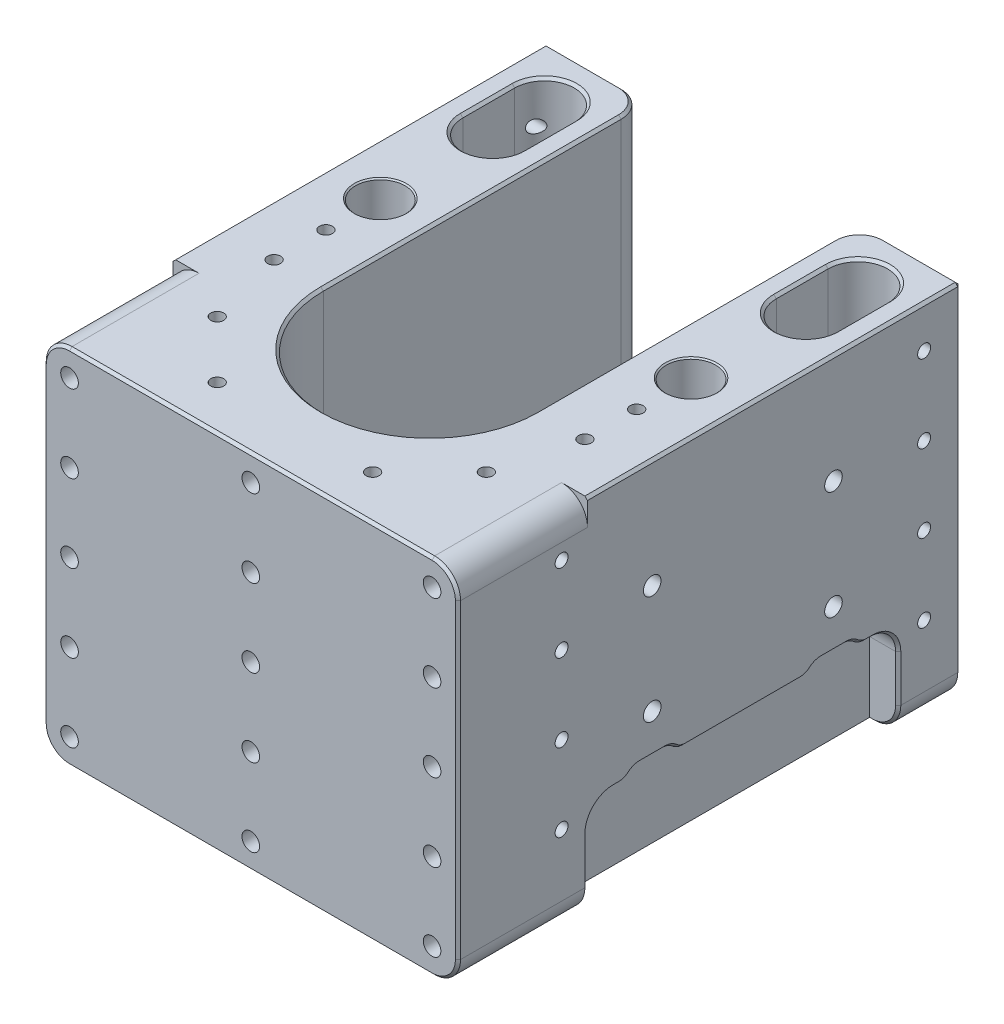
SolidWorks part; units mm, degrees
material "6061-T6 Aluminum"
ref_plane "Front Plane" through (0, 0, 0) normal (0, 0, 1) x (1, 0, 0)
ref_plane "Top Plane" through (0, 0, 0) normal (0, 1, 0) x (1, 0, 0)
ref_plane "Right Plane" through (0, 0, 0) normal (1, 0, 0) x (0, 0, -1)
sketch "Sketch1" plane through (0, 0, 0) normal (0, 1, 0) x (1, 0, 0)
  line L0 (41, 97) -> (80, 97)
  line L1 (-80, -97) -> (80, -97)
  line L2 (-80, -97) -> (-80, 97)
  line L3 (-80, 97) -> (-41, 97)
  line L4 (80, -97) -> (80, 97)
  line L5 (-41, 97) -> (0, 97) construction
  line L6 (0, 97) -> (41, 97) construction
  line L7 (-41, 97) -> (-41, -28)
  line L9 (41, -28) -> (41, 97)
  line L10 (-80, 0) -> (0, 0) construction
  line L11 (0, 0) -> (80, 0) construction
  line L12 (0, -69) -> (0, -97) construction
  arc A2 (-41, -28) -> (41, -28) centre (0, -28) ccw
  point P0 (0, 0)
  dimension "D1" = 160
  dimension "D2" = 194
  dimension "D3" = 28
  dimension "D4" = 82
extrude "Boss-Extrude1" add sketch "Sketch1" along normal blind 140
sketch "Sketch3" plane through (0, 140, 0) normal (0, 1, 0) x (1, 0, 0)
  line L0 (0, 0) -> (0, 13) construction
  line L3 (-60, 13) -> (60, 13) construction
  circle A4 centre (-60, 13) radius 9.55
  circle A5 centre (60, 13) radius 9.55
  dimension "D1" = 13
  dimension "D2" = 120
  dimension "D3" = 19.1
extrude "Cut-Extrude2" cut sketch "Sketch3" against normal blind 14.326 contours A4 | A5 region at (-60, 140, -13) region at (60, 140, -13)
sketch "Sketch8" plane through (80, 0, 0) normal (1, 0, 0) x (0, 0, -1)
  arc A0 (48, 102.25) -> (48, 93.75) centre (48, 98) ccw construction
  arc A1 (-22, 102.25) -> (-22, 93.75) centre (-22, 98) ccw construction
  arc A2 (-22, 60.25) -> (-22, 51.75) centre (-22, 56) ccw construction
  arc A3 (48, 60.25) -> (48, 51.75) centre (48, 56) ccw construction
  arc A4 (48, 102.25) -> (48, 93.75) centre (48, 98) ccw construction
  arc A5 (-22, 102.25) -> (-22, 93.75) centre (-22, 98) ccw construction
  arc A6 (-22, 60.25) -> (-22, 51.75) centre (-22, 56) ccw construction
  arc A7 (48, 60.25) -> (48, 51.75) centre (48, 56) ccw construction
hole_wizard "M8x1.25 Tapped Hole1" positions "Sketch11" profile "Sketch10" tap size "M8x1.25" standard "ANSI Metric"
sketch "Sketch11" plane through (80, 0, 0) normal (1, 0, 0) x (0, 0, -1)
  point P0 (48, 56)
  point P3 (-22, 56)
  point P6 (-22, 98)
  point P9 (48, 98)
cosmetic thread "Hole Thread2" parameters "D1"=25, "D2"=8
cosmetic thread "Hole Thread3" parameters "D1"=25, "D2"=8
cosmetic thread "Hole Thread4" parameters "D1"=25, "D2"=8
cosmetic thread "Hole Thread5" parameters "D1"=25, "D2"=8
sketch "Sketch10" plane through (80, 56, -48) normal (0, 1, 0) x (0, 0, -1)
  line L0 (0, 0) -> (0, 32.0429)
  line L1 (0, 32.0429) -> (3.4, 30)
  line L2 (3.4, 30) -> (3.4, 0)
  line L5 (3.4, 0) -> (0, 0)
  line L10 (0, 32.0429) -> (-3.4, 30) construction
  line L11 (0, -6.35) -> (0, 107.95) construction
  dimension "Tap Drill Dia." = 6.8
  dimension "Tap Drill Depth" = 30
  dimension "Drill Angle" = 118
mirror "Mirror2" about plane through (0, 0, 0) normal (1, 0, 0) of "M8x1.25 Tapped Hole1"
sketch "Sketch33" plane through (0, 0, 97) normal (0, 0, 1) x (1, 0, 0)
  line L0 (-80, 140) -> (-80, 0) construction
  line L1 (-70, 0) -> (70, 0)
  line L2 (-80, 10) -> (-80, 130)
  line L3 (-70, 140) -> (70, 140)
  line L4 (80, 10) -> (80, 130)
  line L5 (-70, 100) -> (-70, 70) construction
  line L6 (-70, 130) -> (-70, 100) construction
  line L7 (-70, 70) -> (-70, 40) construction
  line L8 (-70, 40) -> (-70, 10) construction
  line L9 (-80, 140) -> (80, 140) construction
  arc A0 (-70, 0) -> (-80, 10) centre (-70, 10) cw
  arc A1 (70, 0) -> (80, 10) centre (70, 10) ccw
  arc A2 (70, 140) -> (80, 130) centre (70, 130) cw
  arc A3 (-80, 130) -> (-70, 140) centre (-70, 130) cw
  circle A4 centre (-70, 130) radius 3.375
  circle A5 centre (-70, 100) radius 3.375
  circle A7 centre (-70, 70) radius 3.375
  circle A8 centre (-70, 10) radius 3.375
  circle A9 centre (-70, 40) radius 3.375
  circle A10 centre (0, 130) radius 3.375
  circle A11 centre (70, 130) radius 3.375
  circle A12 centre (0, 100) radius 3.375
  circle A13 centre (70, 100) radius 3.375
  circle A14 centre (0, 70) radius 3.375
  circle A15 centre (70, 70) radius 3.375
  circle A16 centre (0, 40) radius 3.375
  circle A17 centre (70, 40) radius 3.375
  circle A18 centre (70, 10) radius 3.375
  circle A19 centre (0, 10) radius 3.375
  dimension "D2" = 10
  dimension "D3" = 6.75
fillet "Fillet1" radius 10 2 edges at (41, 70, -97) (-41, 70, -97)
sketch "Sketch36" plane through (0, 0, 0) normal (0, 1, 0) x (1, 0, 0)
  line L0 (-69, 13) -> (0, 13) construction
  line L1 (-102.762, 73) -> (-69, 73)
  line L2 (-102.762, 73) -> (-102.762, -47)
  line L3 (-102.762, -47) -> (-69, -47)
  line L4 (-69, 73) -> (-69, -47)
  line L5 (122.5295, 73) -> (69, 73)
  line L6 (122.5295, 73) -> (122.5295, -47)
  line L7 (122.5295, -47) -> (69, -47)
  line L8 (69, 73) -> (69, -47)
  line L9 (0, 13) -> (69, 13) construction
  line L10 (-80, -18.6) -> (-80, -25.4) construction
  line L11 (-80, 51.4) -> (-80, 44.6) construction
  line L12 (-80, -18.6) -> (-80, -25.4) construction
  line L13 (-80, 51.4) -> (-80, 44.6) construction
  line L14 (-80, 44.6) -> (-69, 13) construction
  line L15 (-69, 13) -> (-80, -18.6) construction
  line L16 (0, 13) -> (0, 0) construction
  dimension "D1" = 138
  dimension "D2" = 120
extrude "Cut-Extrude3" cut sketch "Sketch36" along normal blind 38
hole_wizard "CBORE for M8 SHCS1" positions "Sketch31" profile "Sketch32" counterbore size "M8" standard "ANSI Metric" end condition through all
sketch "Sketch31" plane through (0, 0, 0) normal (0, -1, 0) x (-1, 0, 0)
  circle A4 centre (60, 13) radius 9.55 construction
  circle A5 centre (-60, 13) radius 9.55 construction
  point P0 (60, 13)
  point P2 (-60, 13)
sketch "Sketch32" plane through (-60, 0, -13) normal (1, 0, 0) x (0, 0, -1)
  line L0 (0, 0) -> (0, 140)
  line L1 (0, 140) -> (4.5, 140)
  line L3 (4.5, 140) -> (4.5, 9)
  line L4 (4.5, 9) -> (7.5, 9)
  line L5 (7.5, 9) -> (7.5, 0)
  line L7 (7.5, 0) -> (0, 0)
  line L11 (0, -6.35) -> (0, 107.95) construction
  dimension "Thru Hole Dia." = 9
  dimension "Thru Hole Depth" = 140
  dimension "C'Bore Dia." = 15
  dimension "C'Bore Depth" = 9
chamfer "Chamfer7" distance 0.5 angle 45 2 edges at (60, 140, -3.45) (-60, 140, -3.45)
chamfer "Chamfer11" distance 1 angle 45 2 edges at (60, 0, -20.5) (-60, 0, -20.5)
chamfer "Chamfer12" distance 0.5 angle 45 4 edges at (-60, 9, -17.5) (60, 9, -17.5) (-60, 125.674, -8.5) (60, 125.674, -8.5)
sketch "Sketch38" plane through (0, 0, 0) normal (0, -1, 0) x (1, 0, 0)
  circle A0 centre (54, 32.5) radius 4.25 construction
  circle A1 centre (54, 2.5) radius 4.25 construction
  circle A2 centre (54, -27.5) radius 4.25 construction
  circle A3 centre (54, -57.5) radius 4.25 construction
  circle A4 centre (-54, -57.5) radius 4.25 construction
  circle A5 centre (-54, -27.5) radius 4.25 construction
  circle A6 centre (-54, 2.5) radius 4.25 construction
  circle A7 centre (-54, 32.5) radius 4.25 construction
  circle A8 centre (54, 32.5) radius 4.25
  circle A9 centre (54, 2.5) radius 4.25
  circle A10 centre (54, -27.5) radius 4.25
  circle A11 centre (54, -57.5) radius 4.25
  circle A12 centre (-54, -57.5) radius 4.25
  circle A13 centre (-54, -27.5) radius 4.25
  circle A14 centre (-54, 2.5) radius 4.25
  circle A15 centre (-54, 32.5) radius 4.25
sketch "Sketch39" plane through (0, 0, 0) normal (0, -1, 0) x (-1, 0, 0)
  line L0 (-54, -2.5) -> (-54, -32.5) construction
  line L1 (-54, -32.5) -> (-54, -62.5) construction
  line L3 (54, -2.5) -> (54, -32.5) construction
  line L4 (54, -32.5) -> (54, -62.5) construction
  point P0 (54, 57.5)
  point P3 (54, 27.5)
  point P6 (54, -2.5)
  point P9 (54, -32.5)
  point P12 (-54, 57.5)
  point P15 (-54, 27.5)
  point P18 (-54, -2.5)
  point P21 (-54, -32.5)
  point P36 (-54, -62.5)
  point P39 (54, -62.5)
hole_wizard "M8x1.25 Tapped Hole3" positions "Sketch39" profile "Sketch40" tap size "M8x1.25" standard "ANSI Metric"
sketch "Sketch40" plane through (-54, 0, -57.5) normal (1, 0, 0) x (0, 0, -1)
  line L0 (0, 0) -> (0, 22.0429)
  line L1 (0, 22.0429) -> (3.4, 20)
  line L2 (3.4, 20) -> (3.4, 0.9)
  line L3 (3.4, 0.9) -> (4.3, 0)
  line L5 (4.3, 0) -> (0, 0)
  line L6 (-3.4, 0.9) -> (-4.3, 0) construction
  line L10 (0, 22.0429) -> (-3.4, 20) construction
  line L11 (0, -6.35) -> (0, 107.95) construction
  dimension "Tap Drill Dia." = 6.8
  dimension "Tap Drill Depth" = 20
  dimension "Near C'Sink Dia." = 8.6
  dimension "Near C'Sink Angle" = 90
  dimension "Drill Angle" = 118
cosmetic thread "Hole Thread36" parameters "D1"=16, "D2"=8
cosmetic thread "Hole Thread37" parameters "D1"=16, "D2"=8
cosmetic thread "Hole Thread38" parameters "D1"=16, "D2"=8
cosmetic thread "Hole Thread39" parameters "D1"=16, "D2"=8
cosmetic thread "Hole Thread40" parameters "D1"=16, "D2"=8
cosmetic thread "Hole Thread41" parameters "D1"=16, "D2"=8
cosmetic thread "Hole Thread42" parameters "D1"=16, "D2"=8
cosmetic thread "Hole Thread43" parameters "D1"=16, "D2"=8
cosmetic thread "Hole Thread85" parameters "D1"=16, "D2"=8
cosmetic thread "Hole Thread86" parameters "D1"=16, "D2"=8
sketch "Sketch41" plane through (0, 0, 0) normal (0, -1, 0) x (1, 0, 0)
  line L0 (-60, 85) -> (-20, 85) construction
  line L1 (-20, 85) -> (20, 85) construction
  line L2 (20, 85) -> (60, 85) construction
  line L3 (0, 85) -> (0, -13) construction
  line L5 (-60, 85) -> (-60, 65.3183) construction
  circle A0 centre (-60, 85) radius 2.5
  circle A1 centre (-20, 85) radius 2.5
  circle A2 centre (20, 85) radius 2.5
  circle A3 centre (60, 85) radius 2.5
  dimension "D2" = 5
  dimension "D1" = 40
  dimension "D3" = 85
sketch "Sketch42" plane through (0, 0, 0) normal (0, -1, 0) x (-1, 0, 0)
sketch "Sketch44" plane through (0, 0, 0) normal (0, -1, 0) x (-1, 0, 0)
  point P0 (-60, -85)
  point P3 (-20, -85)
  point P6 (20, -85)
  point P9 (60, -85)
hole_wizard "M6x1.0 Tapped Hole1" positions "Sketch44" profile "Sketch43" tap size "M6x1.0" standard "ANSI Metric"
sketch "Sketch43" plane through (60, 0, 85) normal (1, 0, 0) x (0, 0, -1)
  line L0 (0, 0) -> (0, 16.5022)
  line L1 (0, 16.5022) -> (2.5, 15)
  line L2 (2.5, 15) -> (2.5, 0.525)
  line L3 (2.5, 0.525) -> (3.025, 0)
  line L5 (3.025, 0) -> (0, 0)
  line L6 (-2.5, 0.525) -> (-3.025, 0) construction
  line L10 (0, 16.5022) -> (-2.5, 15) construction
  line L11 (0, -6.35) -> (0, 107.95) construction
  dimension "Tap Drill Dia." = 5
  dimension "Tap Drill Depth" = 15
  dimension "Near C'Sink Dia." = 6.05
  dimension "Near C'Sink Angle" = 90
  dimension "Drill Angle" = 118
cosmetic thread "Hole Thread44" parameters "D1"=12, "D2"=6
cosmetic thread "Hole Thread45" parameters "D1"=12, "D2"=6
cosmetic thread "Hole Thread46" parameters "D1"=12, "D2"=6
cosmetic thread "Hole Thread47" parameters "D1"=12, "D2"=6
sketch "Sketch45" plane through (0, 140, 0) normal (0, 1, 0) x (1, 0, 0)
  line L0 (-60.5, 56.9051) -> (-60.5, 76.9051) construction
  line L1 (-72, 56.9051) -> (-72, 76.9051)
  line L2 (-49, 56.9051) -> (-49, 76.9051)
  arc A0 (-72, 56.9051) -> (-49, 56.9051) centre (-60.5, 56.9051) ccw
  arc A1 (-49, 76.9051) -> (-72, 76.9051) centre (-60.5, 76.9051) ccw
  point P2 (-60.5, 66.9051)
  dimension "D3" = 20
extrude "Cut-Extrude4" cut sketch "Sketch45" against normal blind 25
mirror "Mirror3" about plane through (0, 0, 0) normal (1, 0, 0) of "Cut-Extrude4"
fillet "Fillet2" radius 10 4 edges at (74.5, 38, 47) (74.5, 38, -73) (-74.5, 38, 47) (-74.5, 38, -73)
sketch "Sketch46" plane through (0, 0, 97) normal (0, 0, 1) x (1, 0, 0)
  line L0 (-80, 140) -> (80, 140) construction
  line L1 (80, 140) -> (80, 0) construction
  line L2 (70, 140) -> (80, 140)
  line L3 (80, 140) -> (80, 130)
  arc A0 (70, 140) -> (80, 130) centre (70, 130) cw
  dimension "D1" = 10
extrude "Cut-Extrude5" cut sketch "Sketch46" against normal blind 50
mirror "Mirror4" about plane through (0, 0, 0) normal (1, 0, 0) of "Cut-Extrude5"
fillet "Fillet3" radius 10 4 edges at (-80, 0, -85) (80, 0, -85) (80, 0, 72) (-80, 0, 72)
chamfer "Chamfer3" distance 1 angle 45 28 edges at (80, 140, -25) (80, 70, 97) (-60.5, 0, -97) (-80, 70, 97) (-80, 140, -25) (-65.5, 140, -97) (-80, 75, -97) (0, 140, 97) (60.5, 0, -97) (65.5, 140, -97) (43.9289, 0, -94.0711) (43.9289, 140, -94.0711) (41, 0, -29.5) (41, 140, -29.5) (0, 0, 69) (0, 140, 69) (-41, 0, -29.5) (-41, 140, -29.5) (-43.9289, 0, -94.0711) (-43.9289, 140, -94.0711) (0, 0, 97) (80, 75, -97) (77.0711, 137.0711, 97) (77.0711, 2.9289, 97) (-77.0711, 137.0711, 97) (-77.0711, 2.9289, 97) (77.0711, 2.9289, -97) (-77.0711, 2.9289, -97)
chamfer "Chamfer15" distance 1 angle 45 8 edges at (49, 140, -66.9051) (60.5, 140, -88.4051) (60.5, 140, -45.4051) (72, 140, -66.9051) (-72, 140, -66.9051) (-60.5, 140, -45.4051) (-60.5, 140, -88.4051) (-49, 140, -66.9051)
sketch "Sketch55" plane through (69, 0, 0) normal (1, 0, 0) x (0, 0, -1)
  line L0 (63, 38) -> (-37, 38) construction
  line L1 (-32, 30.4123) -> (-12, 30.4123)
  line L2 (-32, 30.4123) -> (-32, 41)
  line L3 (-32, 41) -> (-12, 41)
  line L4 (-12, 30.4123) -> (-12, 41)
  line L5 (-32, 30.4123) -> (-12, 41) construction
  line L6 (-32, 41) -> (-12, 30.4123) construction
  line L7 (38, 30.4123) -> (58, 30.4123)
  line L8 (38, 30.4123) -> (38, 41)
  line L9 (38, 41) -> (58, 41)
  line L10 (58, 30.4123) -> (58, 41)
  line L11 (38, 30.4123) -> (58, 41) construction
  line L12 (38, 41) -> (58, 30.4123) construction
  line L13 (-37, 38) -> (-32, 41) construction
  line L14 (63, 38) -> (58, 41) construction
  point P0 (-22, 35.7062)
  point P5 (48, 35.7062)
  point P14 (37.7281, 41)
  line M9 (63, 38) -> (-37, 38)
  dimension "D1" = 20
  dimension "D2" = 3
  dimension "D3" = 50
extrude "Cut-Extrude6" cut sketch "Sketch55" along normal through all contours L4 L3 L2 M9 | L10 L9 L8 M9 region at (69, 39.5, -48) region at (69, 39.5, 22)
mirror "Mirror6" about plane through (0, 0, 0) normal (1, 0, 0) of "Cut-Extrude6"
fillet "Fillet4" radius 6 8 edges at (74.5, 41, -58) (74.5, 41, -38) (74.5, 41, 32) (74.5, 41, 12) (-74.5, 41, -58) (-74.5, 41, 12) (-74.5, 41, -38) (-74.5, 41, 32)
fillet "Fillet5" radius 6 8 edges at (74.5, 38, -58) (74.5, 38, -38) (74.5, 38, 12) (74.5, 38, 32) (-74.5, 38, -58) (-74.5, 38, -38) (-74.5, 38, 12) (-74.5, 38, 32)
chamfer "Chamfer16" distance 1 angle 45 27 edges at (-69, 0, -13) (69, 0, -13) (-77.0711, 2.9289, -73) (-77.0711, 2.9289, 47) (-80, 19, -73) (-80, 19, 47) (-80, 35.0711, 44.0711) (-80, 38, -61.8706) (-80, 38, 35.8706) (77.0711, 2.9289, -73) (80, 19, -73) (-69.5, 0, -73) (-69.5, 0, 47) (69.5, 0, -73) (-80, 38.3875, 32.6198) (-80, 40.6125, 28.9252) (-80, 41, 22) (-80, 40.6125, 15.0748) (-80, 38.3875, 11.3802) (-80, 38, -13) (-80, 38.3875, -37.3802) (-80, 40.6125, -41.0748) (-80, 41, -48) (-80, 40.6125, -54.9252) (-80, 38.3875, -58.6198) (-80, 35.0711, -70.0711) (80, 35.0711, -70.0711)
hole_wizard "M8x1.25 Tapped Hole4" positions "Sketch47" profile "Sketch48" tap size "M8x1.25" standard "ANSI Metric"
sketch "Sketch47" plane through (0, 0, 97) normal (0, 0, 1) x (1, 0, 0)
  point P0 (-70, 130)
  point P3 (0, 130)
  point P6 (70, 130)
  point P9 (70, 100)
  point P12 (70, 70)
  point P15 (70, 40)
  point P18 (70, 10)
  point P21 (0, 100)
  point P24 (0, 70)
  point P27 (0, 40)
  point P30 (0, 10)
  point P33 (-70, 100)
  point P36 (-70, 70)
  point P39 (-70, 40)
  point P42 (-70, 10)
sketch "Sketch48" plane through (-70, 130, 97) normal (1, 0, 0) x (0, -1, 0)
  line L0 (0, 0) -> (0, 22.0429)
  line L1 (0, 22.0429) -> (3.4, 20)
  line L2 (3.4, 20) -> (3.4, 0)
  line L5 (3.4, 0) -> (0, 0)
  line L10 (0, 22.0429) -> (-3.4, 20) construction
  line L11 (0, -6.35) -> (0, 107.95) construction
  dimension "Tap Drill Dia." = 6.8
  dimension "Tap Drill Depth" = 20
  dimension "Drill Angle" = 118
cosmetic thread "Hole Thread50" parameters "D1"=16, "D2"=8
cosmetic thread "Hole Thread51" parameters "D1"=16, "D2"=8
cosmetic thread "Hole Thread52" parameters "D1"=16, "D2"=8
cosmetic thread "Hole Thread53" parameters "D1"=16, "D2"=8
cosmetic thread "Hole Thread54" parameters "D1"=16, "D2"=8
cosmetic thread "Hole Thread55" parameters "D1"=16, "D2"=8
cosmetic thread "Hole Thread56" parameters "D1"=16, "D2"=8
cosmetic thread "Hole Thread57" parameters "D1"=16, "D2"=8
cosmetic thread "Hole Thread58" parameters "D1"=16, "D2"=8
cosmetic thread "Hole Thread59" parameters "D1"=16, "D2"=8
cosmetic thread "Hole Thread60" parameters "D1"=16, "D2"=8
cosmetic thread "Hole Thread61" parameters "D1"=16, "D2"=8
cosmetic thread "Hole Thread62" parameters "D1"=16, "D2"=8
cosmetic thread "Hole Thread63" parameters "D1"=16, "D2"=8
cosmetic thread "Hole Thread64" parameters "D1"=16, "D2"=8
sketch "Sketch49" plane through (0, 140, 0) normal (0, 1, 0) x (1, 0, 0)
  line L0 (60, -8) -> (60, -28) construction
  line L1 (60, -28) -> (51.9615, -58) construction
  line L2 (51.9615, -58) -> (30, -79.9615) construction
  line L3 (30, -79.9615) -> (0, -88) construction
  circle A0 centre (0, -28) radius 60 construction
  circle A1 centre (0, -88) radius 3
  circle A2 centre (30, -79.9615) radius 3
  circle A3 centre (51.9615, -58) radius 3
  circle A4 centre (60, -28) radius 3
  circle A5 centre (60, -8) radius 3
  circle A6 centre (-30, -79.9615) radius 3
  circle A7 centre (-51.9615, -58) radius 3
  circle A8 centre (-60, -28) radius 3
  circle A9 centre (-60, -8) radius 3
  dimension "D1" = 120
  dimension "D3" = 6
  dimension "D2" = 20
  dimension "D4" = 20
hole_wizard "M6x1.0 Tapped Hole2" positions "Sketch50" profile "Sketch51" tap size "M6x1.0" standard "ANSI Metric"
sketch "Sketch50" plane through (0, 140, 0) normal (0, 1, 0) x (1, 0, 0)
  point P0 (-60, -8)
  point P3 (-60, -28)
  point P6 (-51.9615, -58)
  point P9 (-30, -79.9615)
  point P12 (30, -79.9615)
  point P15 (51.9615, -58)
  point P18 (60, -28)
  point P21 (60, -8)
sketch "Sketch51" plane through (-60, 140, 8) normal (1, 0, 0) x (0, 0, 1)
  line L0 (0, 0) -> (0, 18.5022)
  line L1 (0, 18.5022) -> (2.5, 17)
  line L2 (2.5, 17) -> (2.5, 0)
  line L5 (2.5, 0) -> (0, 0)
  line L10 (0, 18.5022) -> (-2.5, 17) construction
  line L11 (0, -6.35) -> (0, 107.95) construction
  dimension "Tap Drill Dia." = 5
  dimension "Tap Drill Depth" = 17
  dimension "Drill Angle" = 118
cosmetic thread "Hole Thread65" parameters "D1"=12, "D2"=6
cosmetic thread "Hole Thread66" parameters "D1"=12, "D2"=6
cosmetic thread "Hole Thread67" parameters "D1"=12, "D2"=6
cosmetic thread "Hole Thread68" parameters "D1"=12, "D2"=6
cosmetic thread "Hole Thread69" parameters "D1"=12, "D2"=6
cosmetic thread "Hole Thread70" parameters "D1"=12, "D2"=6
cosmetic thread "Hole Thread71" parameters "D1"=12, "D2"=6
cosmetic thread "Hole Thread72" parameters "D1"=12, "D2"=6
sketch "Sketch52" plane through (-80, 0, 0) normal (-1, 0, 0) x (0, 0, 1)
  line L0 (57, 124) -> (57, 94) construction
  line L1 (57, 94) -> (57, 64) construction
  line L2 (57, 64) -> (57, 34) construction
  line L3 (-83, 124) -> (-83, 94) construction
  line L4 (-83, 94) -> (-83, 64) construction
  line L5 (-83, 64) -> (-83, 34) construction
  line L6 (97, 130) -> (97, 10) construction
  line L10 (57, 124) -> (57, 140) construction
  line L11 (47, 140) -> (96, 140) construction
  line L12 (57, 34) -> (57, 4) construction
  line L13 (57, 4) -> (57, -26) construction
  circle A0 centre (-83, 124) radius 3
  circle A1 centre (-83, 94) radius 3
  circle A2 centre (-83, 64) radius 3
  circle A3 centre (-83, 34) radius 3
  circle A4 centre (57, 124) radius 3
  circle A5 centre (57, 94) radius 3
  circle A6 centre (57, 64) radius 3
  circle A7 centre (57, 34) radius 3
  circle A8 centre (57, 4) radius 3
  circle A9 centre (57, -26) radius 3
  circle A10 centre (-83, 4) radius 3
  circle A11 centre (-83, -26) radius 3
  dimension "D1" = 6
  dimension "D2" = 140
  dimension "D3" = 40
  dimension "D4" = 30
  dimension "D5" = 16
hole_wizard "M6x1.0 Tapped Hole3" positions "Sketch53" profile "Sketch54" tap size "M6x1.0" standard "ANSI Metric"
sketch "Sketch53" plane through (-80, 0, 0) normal (-1, 0, 0) x (0, 0, 1)
  point P0 (-83, 124)
  point P3 (-83, 94)
  point P6 (-83, 64)
  point P9 (-83, 34)
  point P12 (57, 124)
  point P15 (57, 94)
  point P18 (57, 64)
  point P21 (57, 34)
  point P37 (0, 0)
  point P38 (0, 0)
  point P39 (0, 0)
sketch "Sketch54" plane through (-80, 124, -83) normal (0, 1, 0) x (0, 0, 1)
  line L0 (0, 0) -> (0, 18.5022)
  line L1 (0, 18.5022) -> (2.5, 17)
  line L2 (2.5, 17) -> (2.5, 0)
  line L5 (2.5, 0) -> (0, 0)
  line L10 (0, 18.5022) -> (-2.5, 17) construction
  line L11 (0, -6.35) -> (0, 107.95) construction
  dimension "Tap Drill Dia." = 5
  dimension "Tap Drill Depth" = 17
  dimension "Drill Angle" = 118
cosmetic thread "Hole Thread73" parameters "D1"=12, "D2"=6
cosmetic thread "Hole Thread74" parameters "D1"=12, "D2"=6
cosmetic thread "Hole Thread75" parameters "D1"=12, "D2"=6
cosmetic thread "Hole Thread76" parameters "D1"=12, "D2"=6
cosmetic thread "Hole Thread77" parameters "D1"=12, "D2"=6
cosmetic thread "Hole Thread78" parameters "D1"=12, "D2"=6
cosmetic thread "Hole Thread79" parameters "D1"=12, "D2"=6
cosmetic thread "Hole Thread80" parameters "D1"=12, "D2"=6
mirror "Mirror5" about plane through (0, 0, 0) normal (1, 0, 0) of "M6x1.0 Tapped Hole3"
